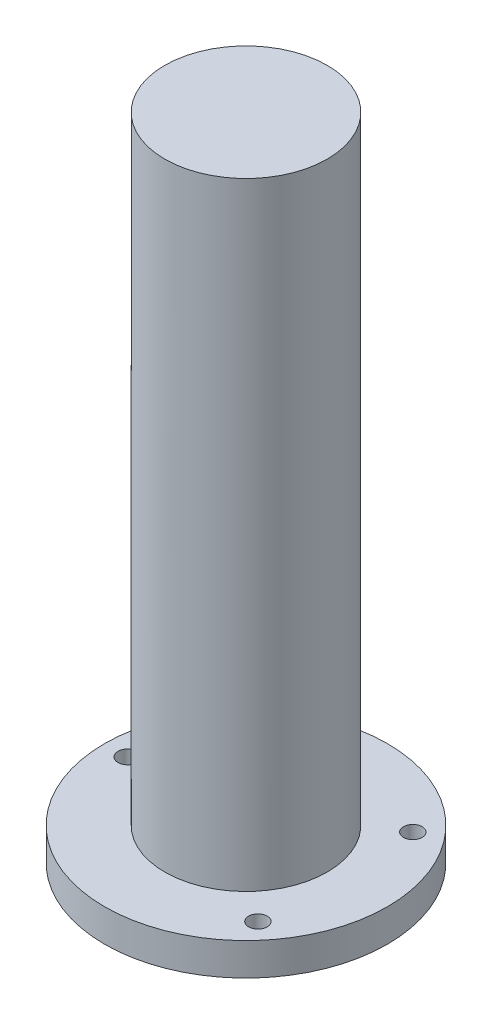
SolidWorks part; units mm, degrees
ref_plane "Front Plane" through (0, 0, 0) normal (0, 0, 1) x (1, 0, 0)
ref_plane "Top Plane" through (0, 0, 0) normal (0, 1, 0) x (1, 0, 0)
ref_plane "Right Plane" through (0, 0, 0) normal (1, 0, 0) x (0, 0, -1)
sketch "Sketch1" plane through (0, 0, 0) normal (0, 1, 0) x (1, 0, 0)
  circle A0 centre (0, 0) radius 22.098
  circle A1 centre (0, 0) radius 9.525
  dimension "D1" = 44.196
  dimension "D2" = 19.05
extrude "Boss-Extrude1" add sketch "Sketch1" along normal blind 5.08 contours A1 | A0 A1 region at (-21.473, 0, 0) region at (0, 0, 0)
sketch "Sketch4" plane through (0, 5.08, 0) normal (0, 1, 0) x (1, 0, 0)
  line L1 (0, 0) -> (59.9509, 0)
  line L2 (0, 0) -> (22.476, 19.4807)
  line L3 (11.238, 9.7404) -> (16.6987, 14.4733)
  circle A1 centre (0, 0) radius 22.098 construction
  circle A3 centre (13.9683, 12.1068) radius 1.4605
  circle A4 centre (13.9683, -12.1068) radius 1.4605
  circle A5 centre (-18.4849, 0) radius 1.524
  dimension "D1" = 18.4849
  dimension "D3" = 2.921
  dimension "D4" = 2.921
  dimension "D6" = 3.048
  dimension "D2" = 40.917
  dimension "D5" = 18.4849
extrude "Cut-Extrude1" cut sketch "Sketch4" against normal blind 58.42 contours A3 | A4 | A5
sketch "Sketch5" plane through (0, 0, 0) normal (0, -1, 0) x (1, 0, 0)
  circle A0 centre (0, 0) radius 12.7
  dimension "D1" = 25.4
extrude "Cut-Extrude2" cut sketch "Sketch5" against normal blind 29.21
extrude "Boss-Extrude2" add sketch "Sketch5<3>" against normal blind 101.6 contours A0
sketch "Sketch5<3>" plane through (0, 0, 0) normal (0, -1, 0) x (1, 0, 0) same geometry as "Sketch5"
sketch "Sketch6" plane through (0, 0, 0) normal (0, -1, 0) x (1, 0, 0)
  circle A0 centre (0, 0) radius 7.62
  dimension "D1" = 15.24
extrude "Cut-Extrude3" cut sketch "Sketch6" against normal blind 17.78
sketch "Sketch7" plane through (0, 0, 0) normal (1, 0, 0) x (0, 0, -1)
  line L0 (0, 0) -> (0, 12.7)
  line L1 (-22.098, 5.08) -> (-22.098, 0)
  line L7 (-7.62, 0) -> (7.62, 0)
  line L8 (-7.62, 0) -> (-7.62, 13.637)
  line L9 (-5.08, 16.177) -> (5.08, 16.177)
  line L10 (7.62, 0) -> (7.62, 13.637)
  line L11 (-7.62, 16.177) -> (7.62, 16.177)
  line L12 (-7.62, 16.177) -> (-7.62, 5.08)
  line L13 (-7.62, 5.08) -> (7.62, 5.08)
  line L14 (7.62, 16.177) -> (7.62, 5.08)
  arc A4 (7.62, 13.637) -> (5.08, 16.177) centre (5.08, 13.637) ccw
  arc A5 (-7.62, 13.637) -> (-5.08, 16.177) centre (-5.08, 13.637) cw
  point P20 (4.4443, 5.08)
  point P23 (4.4443, 12.7)
  dimension "D4" = 2.54
  dimension "D1" = 12.7
  dimension "D2" = 5.08
  dimension "D3" = 7.62
extrude "Cut-Extrude4" cut sketch "Sketch7" against normal through all contours L12 L13 L14 L11
